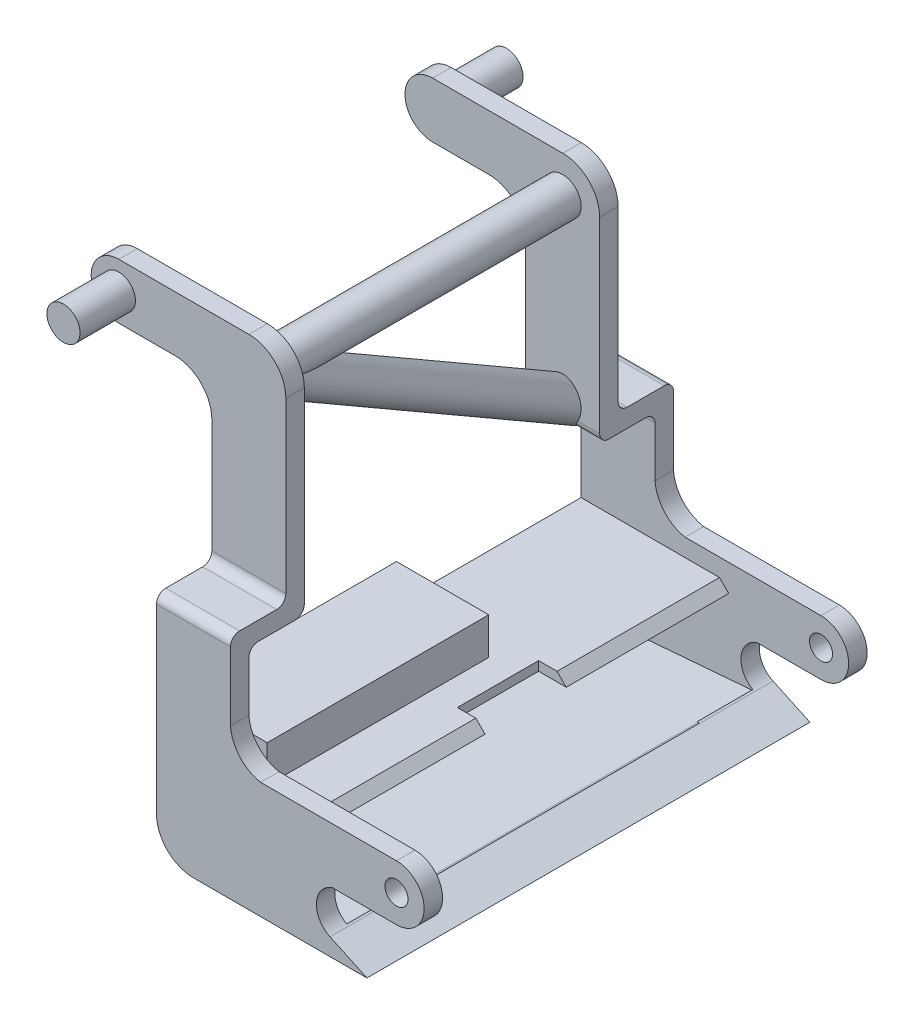
SolidWorks part; units mm, degrees
note: '?' marks a value the reader was unsure of.
ref_plane "Front Plane" through (0, 0, 0) normal (0, 0, 1) x (1, 0, 0)
ref_plane "Top Plane" through (0, 0, 0) normal (0, 1, 0) x (1, 0, 0)
ref_plane "Right Plane" through (0, 0, 0) normal (1, 0, 0) x (0, 0, -1)
sketch "Sketch1" plane through (0, 0, 0) normal (0, 0, 1) x (1, 0, 0)
  line L0 (0, 0) -> (47, 0)
  line L1 (47, 0) -> (37, 4.6631)
  line L3 (-10, 10) -> (-10, 95.0017)
  line L4 (47, 0) -> (55, 0) construction
  line L5 (-35.1979, 120.0017) -> (0.038, 120.0017)
  line L6 (10.0379, 110.027) -> (10.0379, 40.645)
  line L7 (55, 0) -> (55, 24.0017) construction
  line L8 (55, 16.5017) -> (37.5848, 16.5017)
  line L9 (55, 31.5017) -> (18.1852, 31.5017)
  line L11 (-20, 105.0017) -> (-35.1979, 105.0017)
  circle A1 centre (55, 24.0017) radius 3.125
  arc A2 (55, 16.5017) -> (55, 31.5017) centre (55, 24.0017) ccw
  arc A3 (37, 4.6631) -> (37.5848, 16.5017) centre (39.7047, 10.4633) cw
  arc A5 (-35.1979, 120.0017) -> (-35.1979, 105.0017) centre (-35.1979, 112.5017) ccw
  arc A6 (-20, 105.0017) -> (-10, 95.0017) centre (-20, 95.0017) cw
  arc A7 (-10, 10) -> (0, 0) centre (0, 10) ccw
  arc A9 (0.038, 120.0017) -> (10.0379, 110.027) centre (0.038, 110.0017) cw
  arc A10 (10.0379, 40.645) -> (18.1852, 31.5017) centre (20.0142, 41.3331) ccw
  dimension "D4" = 10
  dimension "D9" = 47
  dimension "D10" = 85.0017
  dimension "D11" = 10
  dimension "D13" = 6.25
  dimension "D6" = 25
  dimension "D7" = 6.3998
  dimension "D15" = 35.1979
  dimension "D3" = 10
  dimension "D5" = 7.5
  dimension "D12" = 7.5
  dimension "D16" = 69.382
  dimension "D18" = 10
  dimension "D1" = 10
  dimension "D2" = 8
  dimension "D8" = 17.4152
  dimension "D17" = 20.0379
  dimension "D19" = 36.8148
  dimension "D20" = 12.2465
extrude "Boss-Extrude1" add sketch "Sketch1" along normal blind 120
sketch "Sketch18" plane through (0, 0, 0) normal (0, 0, -1) x (-1, 0, 0)
  line L0 (-0.038, 120.0017) -> (35.1979, 120.0017)
  line L1 (35.1979, 105.0017) -> (20, 105.0017)
  line L2 (-10.0379, 110.027) -> (-10.0379, 61.7017)
  line L3 (-10.0379, 110.027) -> (-10.0379, 40.645) construction
  line L4 (10, 95.0017) -> (10, 61.7017)
  line L5 (10, 10) -> (10, 95.0017) construction
  line L6 (10, 61.7017) -> (-10.0379, 61.7017)
  arc A0 (35.1979, 105.0017) -> (35.1979, 120.0017) centre (35.1979, 112.5017) ccw
  arc A1 (10, 95.0017) -> (20, 105.0017) centre (20, 95.0017) cw
  arc A2 (-10.0379, 110.027) -> (-0.038, 120.0017) centre (-0.038, 110.0017) cw
  circle A3 centre (35.1979, 112.5017) radius 2.5
  dimension "D2" = 5
  dimension "D1" = 58.3
extrude "Cut-Extrude15" cut sketch "Sketch18" against normal blind 15
ref_plane "Plane3" through (0, 0, 60) normal (0, 0, -1) x (-1, 0, 0)
mirror "Mirror1" about plane through (0, 0, 60) normal (0, 0, -1) of "Cut-Extrude15"
ref_plane "Plane1" through (0, 120.0017, 0) normal (0, 1, 0) x (1, 0, 0)
sketch "Sketch2" plane through (0, 120.0017, 0) normal (0, 1, 0) x (1, 0, 0)
  line L0 (-42.6979, -15) -> (-42.6979, -105) construction
  line L1 (-42.6979, -20) -> (62.5843, -20)
  line L2 (-42.6979, -20) -> (-42.6979, -100)
  line L3 (-42.6979, -100) -> (62.5843, -100)
  line L4 (62.5843, -20) -> (62.5843, -100)
  line L5 (-35.1979, -15) -> (0.038, -15) construction
  line L8 (-35.1979, -105) -> (0.038, -105) construction
  dimension "D1" = 5
  dimension "D2" = 105.2822
  dimension "D3" = 5
extrude "Cut-Extrude2" cut sketch "Sketch2" against normal blind 115.3
sketch "Sketch3" plane through (0, 4.7017, 0) normal (0, 1, 0) x (1, 0, 0)
  line L1 (36.5189, -20) -> (-8.4811, -20)
  line L2 (36.5189, -20) -> (36.5189, -100)
  line L3 (36.5189, -100) -> (-8.4811, -100)
  line L4 (-8.4811, -20) -> (-8.4811, -100)
  dimension "D1" = 45
  dimension "D2" = 80
extrude "Cut-Extrude3" cut sketch "Sketch3" against normal blind 3
sketch "Sketch19" plane through (0, 0, 100) normal (0, 0, -1) x (-1, 0, 0)
  line L2 (5.5802, 1.7017) -> (-36.512, 1.7017)
  line L3 (-36.512, 1.7017) -> (-36.512, 4.9167)
  line L4 (-37.5848, 16.5017) -> (-55, 16.5017)
  line L5 (-55, 31.5017) -> (-18.1852, 31.5017)
  line L7 (10, 10) -> (10, 51.7)
  line L8 (10, 10) -> (10, 61.7017) construction
  line L12 (10, 51.7) -> (-10.0379, 51.7)
  line L13 (-10.0379, 61.7017) -> (-10.0379, 40.645) construction
  line L14 (-10.0379, 51.7) -> (-10.0379, 40.645)
  arc A0 (10, 10) -> (5.5802, 1.7017) centre (0, 10) cw
  arc A1 (-37, 4.6631) -> (-37.5848, 16.5017) centre (-39.7047, 10.4633) ccw construction
  arc A2 (-36.512, 4.9167) -> (-37.5848, 16.5017) centre (-39.7047, 10.4633) ccw
  arc A3 (-55, 16.5017) -> (-55, 31.5017) centre (-55, 24.0017) cw
  arc A4 (-55, 31.5017) -> (-55, 16.5017) centre (-55, 24.0017) ccw construction
  arc A5 (-18.1852, 31.5017) -> (-10.0379, 40.645) centre (-20.0142, 41.3331) ccw
  dimension "D2" = 6.3998
  dimension "D3" = 10
  dimension "D1" = 3.2149
  dimension "D4" = 41.7
extrude "Cut-Extrude17" cut sketch "Sketch19" against normal blind 15
mirror "Mirror2" about plane through (0, 0, 60) normal (0, 0, -1) of "Cut-Extrude17"
sketch "Sketch4" plane through (0, 0, 100) normal (0, 0, -1) x (-1, 0, 0)
  line L0 (-30, 26.7017) -> (-30, 1.7017)
  line L1 (-30, 26.7017) -> (10, 26.7017)
  line L2 (10, 51.7) -> (10, 95.0017) construction
  line L3 (10, 26.7017) -> (10, 10)
  line L4 (5.5802, 1.7017) -> (-30, 1.7017)
  line L5 (-36.512, 1.7017) -> (-36.5189, 1.7017) construction
  line L6 (-27.5, 24.2017) -> (7.5, 24.2017)
  line L7 (7.5, 24.2017) -> (7.5, 10)
  line L8 (4.7571, 4.2017) -> (-27.5, 4.2017)
  line L9 (-27.5, 24.2017) -> (-27.5, 4.2017)
  arc A1 (10, 10) -> (5.5802, 1.7017) centre (0, 10) cw
  arc A3 (7.5, 10) -> (4.7571, 4.2017) centre (0, 10) cw
  dimension "D6" = 7.5
  dimension "D7" = 20
  dimension "D1" = 40
  dimension "D2" = 25
  dimension "D4" = 35.5802
  dimension "D5" = 32.2571
  dimension "D3" = 2.5
extrude "Boss-Extrude2" add sketch "Sketch4" along normal blind 95 and the other way blind 15
sketch "Sketch7" plane through (30, 0, 0) normal (1, 0, 0) x (0, 0, -1)
  line L6 (-120, 0) -> (0, 0) construction
  line L7 (-115, 26.7017) -> (-115, 1.7017) construction
  line L8 (-115, 1.7017) -> (-5, 1.7017)
  line L11 (-115, 1.7017) -> (-115, 24.2017)
  line L16 (-115, 24.2017) -> (-5, 24.2017)
  line L17 (-5, 1.7017) -> (-5, 24.2017)
  line L23 (-5, 26.7017) -> (-5, 1.7017) construction
  dimension "D1" = 22.5
  dimension "D2" = 1.7017
extrude "Cut-Extrude13" cut sketch "Sketch7" against normal blind 30
ref_plane "Plane2" through (0, 0, 60) normal (0, 0, 1) x (1, 0, 0)
sketch "Sketch9" plane through (0, 26.7017, 0) normal (0, 1, 0) x (1, 0, 0)
  line L0 (30, -5) -> (30, -115) construction
  line L1 (30, -71) -> (22.5, -71)
  line L2 (30, -71) -> (30, -49)
  line L3 (30, -49) -> (22.5, -49)
  line L4 (22.5, -71) -> (22.5, -49)
  line L5 (18.1852, -20) -> (55, -20) construction
  dimension "D1" = 7.5
  dimension "D2" = 22
  dimension "D3" = 29
extrude "Cut-Extrude14" cut sketch "Sketch9" against normal blind 3
sketch "Sketch10" plane through (0, 0, 100) normal (0, 0, -1) x (-1, 0, 0)
  line L0 (-36.5189, 1.7017) -> (-36.5189, 4.7017)
  line L1 (-36.5189, 4.7017) -> (0.1495, 1.7017)
  line L2 (0.1495, 1.7017) -> (-36.5189, 1.7017)
  dimension "D1" = 4.677
extrude "Boss-Extrude3" add sketch "Sketch10" along normal up to surface and the other way blind 15 up to face at (16.5107, 21.6015, 5)
sketch "Sketch12" plane through (0, 26.7017, 0) normal (0, 1, 0) x (1, 0, 0)
  line L0 (30, -115) -> (30, -71) construction
  line L1 (-10, -115) -> (15, -115)
  line L2 (-10, -115) -> (-10, -55)
  line L3 (-10, -55) -> (15, -55)
  line L4 (15, -115) -> (15, -55)
  line L6 (-10, -5) -> (30, -5) construction
  dimension "D1" = 60
  dimension "D2" = 25
  dimension "D3" = 15
  dimension "D4" = 50
extrude "Boss-Extrude5" add sketch "Sketch12" along normal blind 10
chamfer "Chamfer2" distance 2.5 angle 45 2 edges at (30, 26.7017, 27) (30, 26.7017, 93)
sketch "Sketch20" plane through (0, 0, 100) normal (0, 0, -1) x (-1, 0, 0)
  circle A0 centre (-0.038, 110.0017) radius 5
  arc A1 (-0.038, 120.0017) -> (-10.0379, 110.027) centre (-0.038, 110.0017) ccw construction
  circle A2 centre (-0.038, 110.0017) radius 3.4914
  dimension "D1" = 10
  dimension "D2" = 6.9828
extrude "Boss-Extrude8" add sketch "Sketch20" along normal up to surface (80 mm away) up to face at (36.6149, 4.7544, 20)
ref_axis "Axis1" through (0.038, 110.0017, 20) along (0, 0, 1)?
ref_axis "Axis2" through (-42.6979, 112.5017, 100) along (1, 0, 0)?
ref_plane "Plane4" through (0, 71.4267, 123.7147) normal (0, -0.5, -0.866) x (1, 0, 0)
sketch "Sketch22" plane through (0, 71.4267, 123.7147) normal (0, -0.5, -0.866) x (1, 0, 0)
  circle A0 centre (0, -44.0931) radius 5
  circle A1 centre (0, -44.0931) radius 3.5
  dimension "D1" = 10
  dimension "D2" = 7
extrude "Boss-Extrude10" add sketch "Sketch22" along normal up to surface (91.4155 mm away)
sketch "Sketch23" plane through (10.0379, 0, 0) normal (1, 0, 0) x (0, 0, -1)
  line L1 (-100, 51.7) -> (-115, 51.7)
  line L2 (-100, 51.7) -> (-100, 56.7)
  line L3 (-100, 56.7) -> (-115, 56.7)
  line L4 (-115, 51.7) -> (-115, 56.7)
  dimension "D1" = 5
  dimension "D2" = 15
extrude "Cut-Extrude18" cut sketch "Sketch23" against normal through all
mirror "Mirror3" about plane through (0, 0, 60) normal (0, 0, -1) of "Cut-Extrude18"
fillet "Fillet1" radius 2.5 7 edges at (5.1814, 56.7, 20) (-5.1624, 56.7, 20) (0.019, 56.7, 100) (0.019, 56.7, 115) (0.019, 56.7, 5) (0.019, 61.7017, 0) (0.019, 61.7017, 120)
sketch "Sketch24" plane through (0, 0, 120) normal (0, 0, 1) x (1, 0, 0)
  circle A0 centre (-35.1979, 112.5017) radius 2.5223
extrude "Cut-Extrude19" cut sketch "Sketch24" against normal blind 15
mirror "Mirror4" about plane through (0, 0, 60) normal (0, 0, 1) of "Cut-Extrude19"
sketch "Sketch25" plane through (0, 0, 105) normal (0, 0, 1) x (1, 0, 0)
  circle A0 centre (-35.1979, 112.5017) radius 4.5
  dimension "D1" = 9
extrude "Boss-Extrude11" add sketch "Sketch25" along normal blind 15
sketch "Sketch26" plane through (0, 0, 15) normal (0, 0, -1) x (-1, 0, 0)
  circle A0 centre (35.1979, 112.5017) radius 4.5
  dimension "D1" = 9
extrude "Boss-Extrude12" add sketch "Sketch26" along normal blind 15
sketch "Sketch27" plane through (0, 0, 0) normal (0, 0, -1) x (-1, 0, 0)
  circle A0 centre (35.1979, 112.5017) radius 2.5
  dimension "D1" = 5
extrude "Cut-Extrude20" cut sketch "Sketch27" against normal blind 15
fillet "Fillet2" radius 2.5 2 edges at (0.019, 61.7017, 105) (0.019, 61.7017, 15)
